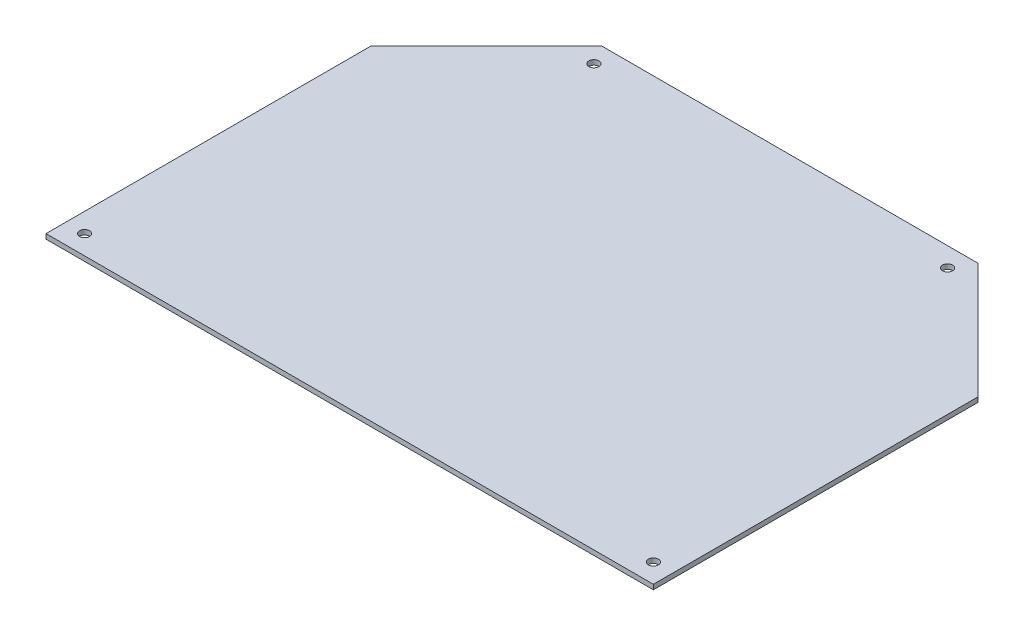
SolidWorks part; units mm, degrees
note: The reader was unsure of these and kept them because the rebuilt part matched: thickness of "Base-Flange1", "Sheet-Metal1", "Sheet-Metal2", "Sheet-Metal3".
ref_plane "Front" through (0, 0, 0) normal (0, 0, 1) x (1, 0, 0)
ref_plane "Top" through (0, 0, 0) normal (0, 1, 0) x (1, 0, 0)
ref_plane "Right" through (0, 0, 0) normal (1, 0, 0) x (0, 0, -1)
sketch "Sketch2"
  line L1 (-200, -145) -> (200, -145)
  line L2 (-200, -145) -> (-200, 145)
  line L3 (-200, 145) -> (200, 145)
  line L4 (200, -145) -> (200, 145)
  line L5 (-200, -145) -> (200, 145) construction
  line L6 (-200, 145) -> (200, -145) construction
  point P0 (0, 0)
  dimension "D1" = 400
  dimension "D2" = 290
base flange "Base-Flange1" sketch "Sketch2" thickness 3.175 reverse thickness direction no parameters "D1"=0.7366
sketch "Sketch10" plane through (0, 0, 0) normal (0, 1, 0) x (1, 0, 0)
  line L0 (200, 68.8) -> (200, 145)
  line L1 (200, -145) -> (200, 145) construction
  line L2 (200, 145) -> (123.8, 145)
  line L3 (200, 145) -> (-200, 145) construction
  line L4 (123.8, 145) -> (200, 68.8)
  line L5 (-200, 145) -> (-123.8, 145)
  line L6 (-123.8, 145) -> (-200, 68.8)
  line L7 (-200, 145) -> (-200, -145) construction
  line L8 (-200, 68.8) -> (-200, 145)
  dimension "D1" = 76.2
extrude "Cut-Extrude1" cut sketch "Sketch10" against normal blind 10
hole_wizard "M6 Clearance Hole1" positions "Sketch7" profile "Sketch8" hole size "M6" standard "ANSI Metric"
sketch "Sketch7" plane through (0, 0, 0) normal (0, 1, 0) x (1, 0, 0)
  line L11 (187.3, -132.3) -> (-187.3, -132.3) construction
  line L13 (0, 0) -> (0, -132.3) construction
  line L15 (0, 0) -> (0, 132.3) construction
  line L17 (116.4677, 132.3) -> (-116.4677, 132.3) construction
  line L19 (123.8, 145) -> (116.4677, 132.3) construction
  line L22 (123.8, 145) -> (-123.8, 145) construction
  line L23 (-200, 68.8) -> (-200, -145) construction
  line L24 (-200, -145) -> (200, -145) construction
  point P0 (-187.3, -132.3)
  point P6 (187.3, -132.3)
  point P58 (116.4677, 132.3)
  point P60 (-116.4677, 132.3)
  dimension "D1" = 60
  dimension "D2" = 12.7
  dimension "D3" = 12.7
  dimension "D4" = 12.7
sketch "Sketch8" plane through (-187.3, 0, 132.3) normal (1, 0, 0) x (0, 0, 1)
  line L0 (0, 0) -> (0, 20.7328)
  line L1 (0, 20.7328) -> (3.3, 18.75)
  line L2 (3.3, 18.75) -> (3.3, 0)
  line L5 (3.3, 0) -> (0, 0)
  line L10 (0, 20.7328) -> (-3.3, 18.75) construction
  line L11 (0, -6.35) -> (0, 107.95) construction
  dimension "Hole Dia." = 6.6
  dimension "Hole Depth" = 18.75
  dimension "Drill Angle" = 118
sketch "Bend-Lines1" [suppressed] plane through (0, 0, 0) normal (0, 1, 0) x (1, 0, 0)
sketch "Bounding-Box1" [suppressed] plane through (0, 0, 0) normal (0, 1, 0) x (1, 0, 0)
sheet metal parameters "Sheet-Metal1" thickness 3.175 parameters "D1"=0.7366, "D7"=0.7366
flat pattern "Flat-Pattern1" [suppressed]
sketch "Bend-Lines2" plane through (0, 0, 0) normal (0, 1, 0) x (1, 0, 0)
sketch3d "Bounding-Box2" [suppressed]
  line L0 (203.2, 127, 0) -> (-203.2, 127, 0) construction
  line L1 (203.2, -127, 0) -> (-203.2, -127, 0) construction
  line L2 (203.2, 127, 0) -> (203.2, -127, 0) construction
  line L3 (-203.2, 127, 0) -> (-203.2, -127, 0) construction
sheet metal parameters "Sheet-Metal2" thickness 3.175 parameters "D1"=0.7366, "D7"=0.7366
flat pattern "Flat-Pattern1"
sketch "Bend-Lines2" plane through (0, 0, 0) normal (0, 1, 0) x (1, 0, 0)
sketch3d "Bounding-Box2" [suppressed]
  line L0 (200, 145, 0) -> (-200, 145, 0) construction
  line L1 (200, -145, 0) -> (-200, -145, 0) construction
  line L2 (200, 145, 0) -> (200, -145, 0) construction
  line L3 (-200, 145, 0) -> (-200, -145, 0) construction
sheet metal parameters "Sheet-Metal3" thickness 3.175 parameters "D1"=0.7366, "D7"=0.7366
flat pattern "Flat-Pattern1"
sketch "Bend-Lines2" plane through (0, 0, 0) normal (0, 1, 0) x (1, 0, 0)
sketch3d "Bounding-Box2" [suppressed]
  line L0 (203.2, 127, 0) -> (-203.2, 127, 0) construction
  line L1 (203.2, -127, 0) -> (-203.2, -127, 0) construction
  line L2 (203.2, 127, 0) -> (203.2, -127, 0) construction
  line L3 (-203.2, 127, 0) -> (-203.2, -127, 0) construction
